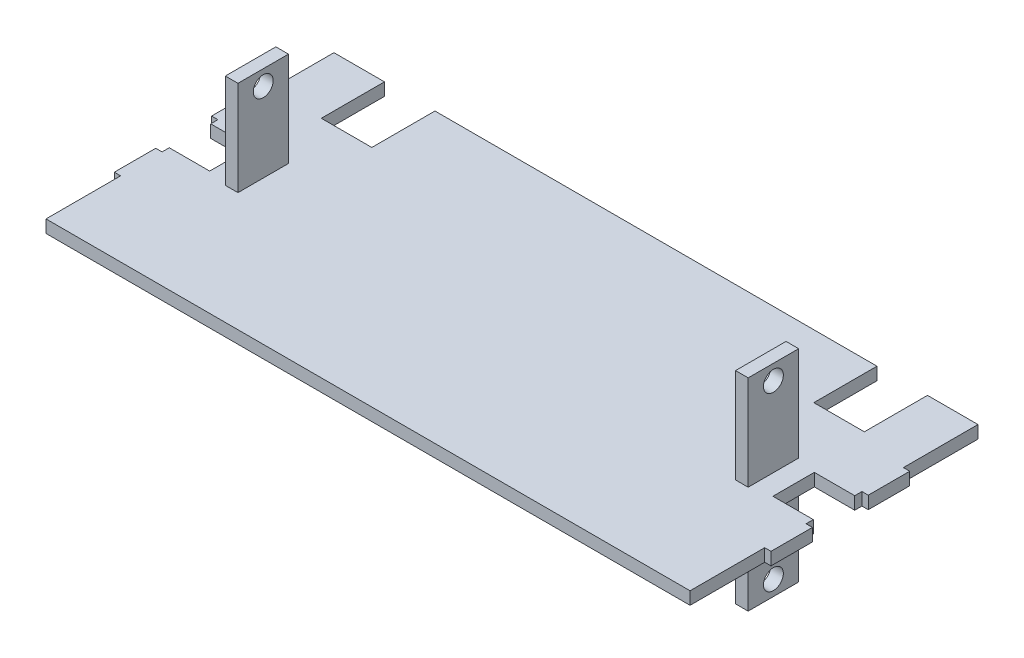
SolidWorks part; units mm, degrees
ref_plane "Front Plane" through (0, 0, 0) normal (0, 0, 1) x (1, 0, 0)
ref_plane "Top Plane" through (0, 0, 0) normal (0, 1, 0) x (1, 0, 0)
ref_plane "Right Plane" through (0, 0, 0) normal (1, 0, 0) x (0, 0, -1)
sketch "Sketch1" plane through (0, 0, 0) normal (0, 1, 0) x (1, 0, 0)
  line L0 (0, 72.39) -> (0, -72.39) construction
  line L1 (161.925, -72.39) -> (-161.925, -72.39)
  line L2 (161.925, -72.39) -> (161.925, -34.8747)
  line L3 (161.925, 72.39) -> (136.525, 72.39)
  line L4 (-161.925, -72.39) -> (-161.925, -34.8747)
  line L5 (161.925, -72.39) -> (-161.925, 72.39) construction
  line L6 (161.925, 72.39) -> (-161.925, -72.39) construction
  line L7 (161.925, 10.414) -> (141.605, 10.414)
  line L9 (161.925, -10.414) -> (141.605, -10.414)
  line L10 (141.605, 10.414) -> (141.605, -10.414)
  line L11 (-136.525, 72.39) -> (-161.925, 72.39)
  line L13 (-161.925, -10.414) -> (-141.605, -10.414)
  line L14 (-141.605, 10.414) -> (-141.605, -10.414)
  line L15 (-161.925, 10.414) -> (-141.605, 10.414)
  line L17 (-127, 0) -> (127, 0) construction
  line L18 (-161.925, 14.0467) -> (-165.1, 14.0467)
  line L20 (-161.925, 34.8747) -> (-165.1, 34.8747)
  line L21 (-165.1, 14.0467) -> (-165.1, 34.8747)
  line L22 (-161.925, -34.8747) -> (-165.1, -34.8747)
  line L23 (-165.1, -14.0467) -> (-165.1, -34.8747)
  line L24 (-161.925, -14.0467) -> (-165.1, -14.0467)
  line L27 (161.925, -14.0467) -> (165.1, -14.0467)
  line L28 (165.1, -14.0467) -> (165.1, -34.8747)
  line L29 (161.925, -34.8747) -> (165.1, -34.8747)
  line L30 (161.925, 34.8747) -> (165.1, 34.8747)
  line L31 (165.1, 14.0467) -> (165.1, 34.8747)
  line L32 (161.925, 14.0467) -> (165.1, 14.0467)
  line L34 (-161.925, 34.8747) -> (-161.925, 72.39)
  line L35 (-161.925, -14.0467) -> (-161.925, -10.414)
  line L36 (161.925, 34.8747) -> (161.925, 72.39)
  line L37 (161.925, -14.0467) -> (161.925, -10.414)
  line L38 (-161.925, 10.414) -> (-161.925, 14.0467)
  line L39 (161.925, 10.414) -> (161.925, 14.0467)
  line L40 (-136.525, 72.39) -> (-136.525, 40.64)
  line L41 (-136.525, 40.64) -> (-111.125, 40.64)
  line L42 (-111.125, 72.39) -> (-111.125, 40.64)
  line L44 (111.125, 72.39) -> (111.125, 40.64)
  line L45 (111.125, 40.64) -> (136.525, 40.64)
  line L46 (136.525, 72.39) -> (136.525, 40.64)
  line L47 (111.125, 72.39) -> (-111.125, 72.39)
  point P0 (0, 0)
  point P6 (127, 0)
  dimension "D1" = 323.85
  dimension "D2" = 144.78
  dimension "D3" = 20.828
  dimension "D5" = 3.175
  dimension "D6" = 20.828
  dimension "D4" = 20.32
  dimension "D7" = 31.75
  dimension "D8" = 25.4
  dimension "D9" = 25.4
  dimension "D10" = 31.75
  dimension "D12" = 25.4
  dimension "D11" = 25.4
extrude "Boss-Extrude1" add sketch "Sketch1" along normal mid plane 6.35
sketch "Sketch2" plane through (0, 0, 0) normal (0, 1, 0) x (1, 0, 0)
  line L0 (-141.605, 10.414) -> (-141.605, -10.414) construction
  line L1 (125.095, -12.7) -> (131.445, -12.7)
  line L2 (125.095, -12.7) -> (125.095, 12.7)
  line L3 (125.095, 12.7) -> (131.445, 12.7)
  line L4 (131.445, -12.7) -> (131.445, 12.7)
  line L5 (125.095, -12.7) -> (131.445, 12.7) construction
  line L6 (125.095, 12.7) -> (131.445, -12.7) construction
  line L9 (-125.095, -12.7) -> (-125.095, 12.7)
  line L10 (-125.095, 12.7) -> (-131.445, 12.7)
  line L11 (-131.445, -12.7) -> (-131.445, 12.7)
  line L12 (-125.095, -12.7) -> (-131.445, -12.7)
  line L13 (141.605, -10.414) -> (141.605, 10.414) construction
  point P0 (128.27, 0)
  point P10 (141.605, 0)
  dimension "D1" = 10.16
  dimension "D2" = 10.16
  dimension "D3" = 25.4
  dimension "D4" = 25.4
  dimension "D5" = 6.35
  dimension "D6" = 6.35
  dimension "D7" = 6.35
extrude "Boss-Extrude2" add sketch "Sketch2" along normal mid plane 101.6
sketch "Sketch3" plane through (-131.445, 0, 0) normal (-1, 0, 0) x (0, 0, 1)
  line L0 (-12.7, 50.8) -> (12.7, 50.8) construction
  line L1 (-12.7, -50.8) -> (12.7, -50.8) construction
  circle A0 centre (0, 43.18) radius 5.0038
  circle A1 centre (0, -43.18) radius 5.0038
  point P4 (0, 50.8)
  dimension "D1" = 10.0076
  dimension "D2" = 10.0076
  dimension "D3" = 7.62
  dimension "D4" = 7.62
  dimension "D5" = 86.36
extrude "Cut-Extrude1" cut sketch "Sketch3" against normal through all both and the other way through all
equation "\"length\"= 12.75"
equation "\"width\"= 5.7"
equation "\"height\"= 0.25"
equation "\"D1@Sketch1\"=\"length\""
equation "\"D2@Sketch1\"=\"width\""
equation "\"eyebolt width\"= 0.82"
equation "\"eyebolt length\"= 0.8"
equation "\"D3@Sketch1\"=\"eyebolt width\""
equation "\"D4@Sketch1\"=\"eyebolt length\""
equation "\"lead screw holder height\"= 2.76"
equation "\"lead screw diameter\"=0.394"
equation "\"D1@Sketch3\"=\"lead screw diameter\""
equation "\"distance from holders to board\"=0.4"
equation "\"D2@Sketch3\"=\"lead screw diameter\""
equation "\"lead_screw_dist\"=3.4"
equation "\"D5@Sketch3\"=\"lead_screw_dist\""
